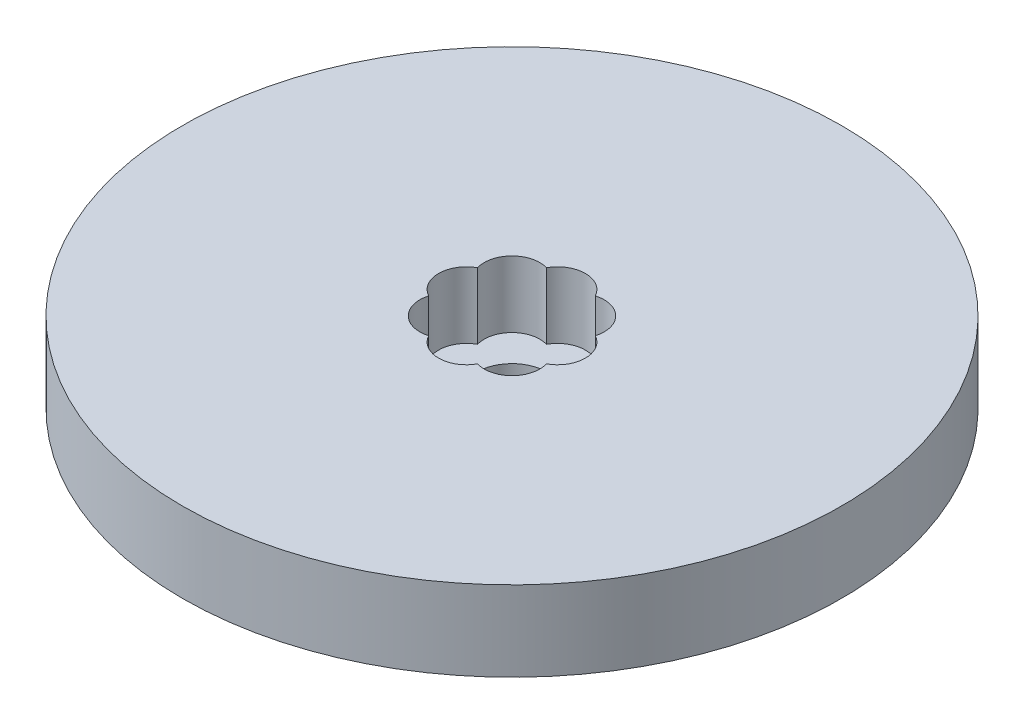
SolidWorks part; units mm, degrees
ref_plane "Front Plane" through (0, 0, 0) normal (0, 0, 1) x (1, 0, 0)
ref_plane "Top Plane" through (0, 0, 0) normal (0, 1, 0) x (1, 0, 0)
ref_plane "Right Plane" through (0, 0, 0) normal (1, 0, 0) x (0, 0, -1)
sketch "Sketch1" plane through (0, 0, 0) normal (0, 1, 0) x (1, 0, 0)
  circle A0 centre (0, 0) radius 70
  dimension "FLANGE_OD" = 140
extrude "Boss-Extrude1" add sketch "Sketch1" along normal blind 17
sketch "Sketch2" plane through (0, 0, 0) normal (0, 1, 0) x (1, 0, 0)
  circle A0 centre (0, 0) radius 7.5
  dimension "BORE_D" = 15
extrude "Cut-Extrude1" cut sketch "Sketch2" along normal through all
sketch "Sketch3" plane through (0, 17, 0) normal (0, 1, 0) x (1, 0, 0)
  circle A0 centre (0, 0) radius 9.6764 construction
  circle A1 centre (-9.6764, 0) radius 5.906
  dimension "BOLT_D" = 11.8121
  dimension "BOLT_PCD" = 19.3527
extrude "Cut-Extrude2" cut sketch "Sketch3" against normal blind 14.0973
pattern_circular "CirPattern1" count 8 over 360 about axis through (0, 0, 0) along (0, 1, 0) of "Cut-Extrude2"
